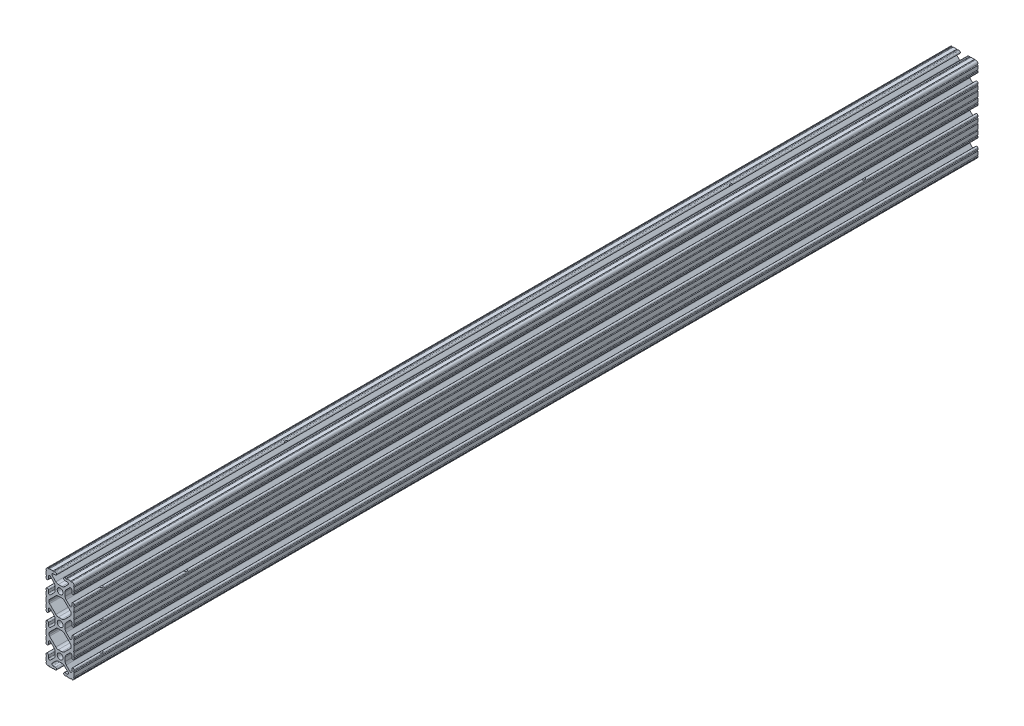
SolidWorks part; units mm, degrees
ref_plane "Front" through (0, 0, 0) normal (0, 0, 1) x (1, 0, 0)
ref_plane "Top" through (0, 0, 0) normal (0, 1, 0) x (1, 0, 0)
ref_plane "Right" through (0, 0, 0) normal (1, 0, 0) x (0, 0, -1)
sketch "Sketch1" plane through (0, 0, 0) normal (0, 0, 1) x (1, 0, 0)
  line L0 (-7.4908, -34.8742) -> (7.4908, -34.8742) construction
  line L1 (-3.1974, -36.9951) -> (3.1974, -36.9951) construction
  line L2 (-7.4908, 34.8742) -> (7.4908, 34.8742) construction
  line L3 (-3.1974, 36.9951) -> (3.1974, 36.9951) construction
  line L16 (-9.9314, -12.1463) -> (-9.9314, -13.2537)
  line L17 (-3.8759, -5.4384) -> (-9.4702, -11.0327)
  line L18 (1.6308, -4.5085) -> (-1.6308, -4.5085)
  line L19 (9.4702, -11.0327) -> (3.8759, -5.4384)
  line L20 (9.9314, -13.2537) -> (9.9314, -12.1463)
  line L21 (3.8759, -19.9616) -> (9.4702, -14.3673)
  line L22 (-1.6308, -20.8915) -> (1.6308, -20.8915)
  line L23 (-9.4702, -14.3673) -> (-3.8759, -19.9616)
  line L32 (-9.9314, 13.2537) -> (-9.9314, 12.1463)
  line L33 (-3.8759, 19.9616) -> (-9.4702, 14.3673)
  line L34 (1.6308, 20.8915) -> (-1.6308, 20.8915)
  line L35 (9.4702, 14.3673) -> (3.8759, 19.9616)
  line L36 (9.9314, 12.1463) -> (9.9314, 13.2537)
  line L37 (3.8759, 5.4384) -> (9.4702, 11.0327)
  line L38 (-1.6308, 4.5085) -> (1.6308, 4.5085)
  line L39 (-9.4702, 11.0327) -> (-3.8759, 5.4384)
  line L152 (-12.7, 34.9504) -> (-12.7, 31.7246)
  line L153 (-12.7, 30.7086) -> (-12.7, 29.7023)
  line L154 (-10.4902, 29.7023) -> (-10.4902, 31.8748)
  line L155 (-8.7558, 32.5932) -> (-5.4384, 29.2759)
  line L156 (-4.5085, 27.0308) -> (-4.5085, 23.7692)
  line L157 (-5.4384, 21.5241) -> (-8.7558, 18.2068)
  line L158 (-10.4902, 18.9252) -> (-10.4902, 21.0977)
  line L159 (-12.7, 21.0977) -> (-12.7, 20.0914)
  line L160 (-12.7, 19.0754) -> (-12.7, 15.8496)
  line L161 (-12.7, 14.8336) -> (-12.7, 10.5664)
  line L162 (-12.7, 9.5504) -> (-12.7, 6.3246)
  line L163 (-12.7, 5.3086) -> (-12.7, 4.3023)
  line L164 (-10.4902, 4.3023) -> (-10.4902, 6.4748)
  line L165 (-8.7558, 7.1932) -> (-5.4384, 3.8759)
  line L166 (-4.5085, 1.6308) -> (-4.5085, -1.6308)
  line L167 (-5.4384, -3.8759) -> (-8.7558, -7.1932)
  line L168 (-10.4902, -6.4748) -> (-10.4902, -4.3023)
  line L169 (-12.7, -4.3023) -> (-12.7, -5.3086)
  line L170 (-12.7, -6.3246) -> (-12.7, -9.5504)
  line L171 (-12.7, -10.5664) -> (-12.7, -14.8336)
  line L172 (-12.7, -15.8496) -> (-12.7, -19.0754)
  line L173 (-12.7, -20.0914) -> (-12.7, -21.0977)
  line L174 (-10.4902, -21.0977) -> (-10.4902, -18.9252)
  line L175 (-8.7558, -18.2068) -> (-5.4384, -21.5241)
  line L176 (-4.5085, -23.7692) -> (-4.5085, -27.0308)
  line L177 (-5.4384, -29.2759) -> (-8.7558, -32.5932)
  line L178 (-10.4902, -31.8748) -> (-10.4902, -29.7023)
  line L179 (-12.7, -29.7023) -> (-12.7, -30.7086)
  line L180 (-12.7, -31.7246) -> (-12.7, -34.9504)
  line L181 (-9.5504, -38.1) -> (-6.3246, -38.1)
  line L182 (-5.3086, -38.1) -> (-4.3023, -38.1)
  line L183 (-4.3023, -35.8902) -> (-6.4748, -35.8902)
  line L184 (-7.1932, -34.1558) -> (-3.8759, -30.8384)
  line L185 (-1.6308, -29.9085) -> (1.6308, -29.9085)
  line L186 (3.8759, -30.8384) -> (7.1932, -34.1558)
  line L187 (6.4748, -35.8902) -> (4.3023, -35.8902)
  line L188 (4.3023, -38.1) -> (5.3086, -38.1)
  line L189 (6.3246, -38.1) -> (9.5504, -38.1)
  line L190 (12.7, -34.9504) -> (12.7, -31.7246)
  line L191 (12.7, -30.7086) -> (12.7, -29.7023)
  line L192 (10.4902, -29.7023) -> (10.4902, -31.8748)
  line L193 (8.7558, -32.5932) -> (5.4384, -29.2759)
  line L194 (4.5085, -27.0308) -> (4.5085, -23.7692)
  line L195 (5.4384, -21.5241) -> (8.7558, -18.2068)
  line L196 (10.4902, -18.9252) -> (10.4902, -21.0977)
  line L197 (12.7, -21.0977) -> (12.7, -20.0914)
  line L198 (12.7, -19.0754) -> (12.7, -15.8496)
  line L199 (12.7, -14.8336) -> (12.7, -10.5664)
  line L200 (12.7, -9.5504) -> (12.7, -6.3246)
  line L201 (12.7, -5.3086) -> (12.7, -4.3023)
  line L202 (10.4902, -4.3023) -> (10.4902, -6.4748)
  line L203 (8.7558, -7.1932) -> (5.4384, -3.8759)
  line L204 (4.5085, -1.6308) -> (4.5085, 1.6308)
  line L205 (5.4384, 3.8759) -> (8.7558, 7.1932)
  line L206 (10.4902, 6.4748) -> (10.4902, 4.3023)
  line L207 (12.7, 4.3023) -> (12.7, 5.3086)
  line L208 (12.7, 6.3246) -> (12.7, 9.5504)
  line L209 (12.7, 10.5664) -> (12.7, 14.8336)
  line L210 (12.7, 15.8496) -> (12.7, 19.0754)
  line L211 (12.7, 20.0914) -> (12.7, 21.0977)
  line L212 (10.4902, 21.0977) -> (10.4902, 18.9252)
  line L213 (8.7558, 18.2068) -> (5.4384, 21.5241)
  line L214 (4.5085, 23.7692) -> (4.5085, 27.0308)
  line L215 (5.4384, 29.2759) -> (8.7558, 32.5932)
  line L216 (10.4902, 31.8748) -> (10.4902, 29.7023)
  line L217 (12.7, 29.7023) -> (12.7, 30.7086)
  line L218 (12.7, 31.7246) -> (12.7, 34.9504)
  line L219 (9.5504, 38.1) -> (6.3246, 38.1)
  line L220 (5.3086, 38.1) -> (4.3023, 38.1)
  line L221 (4.3023, 35.8902) -> (6.4748, 35.8902)
  line L222 (7.1932, 34.1558) -> (3.8759, 30.8384)
  line L223 (1.6308, 29.9085) -> (-1.6308, 29.9085)
  line L224 (-3.8759, 30.8384) -> (-7.1932, 34.1558)
  line L225 (-6.4748, 35.8902) -> (-4.3023, 35.8902)
  line L226 (-4.3023, 38.1) -> (-5.3086, 38.1)
  line L227 (-6.3246, 38.1) -> (-9.5504, 38.1)
  circle A2 centre (0, -25.4) radius 2.6035
  circle A4 centre (0, 0) radius 2.6035
  circle A6 centre (0, 25.4) radius 2.6035
  arc A18 (-9.9314, -13.2537) -> (-9.4702, -14.3673) centre (-8.3566, -13.2537) ccw
  arc A19 (-9.4702, -11.0327) -> (-9.9314, -12.1463) centre (-8.3566, -12.1463) ccw
  arc A20 (-1.6308, -4.5085) -> (-3.8759, -5.4384) centre (-1.6308, -7.6835) ccw
  arc A21 (3.8759, -5.4384) -> (1.6308, -4.5085) centre (1.6308, -7.6835) ccw
  arc A22 (9.9314, -12.1463) -> (9.4702, -11.0327) centre (8.3566, -12.1463) ccw
  arc A23 (9.4702, -14.3673) -> (9.9314, -13.2537) centre (8.3566, -13.2537) ccw
  arc A24 (1.6308, -20.8915) -> (3.8759, -19.9616) centre (1.6308, -17.7165) ccw
  arc A25 (-3.8759, -19.9616) -> (-1.6308, -20.8915) centre (-1.6308, -17.7165) ccw
  arc A36 (-9.9314, 12.1463) -> (-9.4702, 11.0327) centre (-8.3566, 12.1463) ccw
  arc A37 (-9.4702, 14.3673) -> (-9.9314, 13.2537) centre (-8.3566, 13.2537) ccw
  arc A38 (-1.6308, 20.8915) -> (-3.8759, 19.9616) centre (-1.6308, 17.7165) ccw
  arc A39 (3.8759, 19.9616) -> (1.6308, 20.8915) centre (1.6308, 17.7165) ccw
  arc A40 (9.9314, 13.2537) -> (9.4702, 14.3673) centre (8.3566, 13.2537) ccw
  arc A41 (9.4702, 11.0327) -> (9.9314, 12.1463) centre (8.3566, 12.1463) ccw
  arc A42 (1.6308, 4.5085) -> (3.8759, 5.4384) centre (1.6308, 7.6835) ccw
  arc A43 (-3.8759, 5.4384) -> (-1.6308, 4.5085) centre (-1.6308, 7.6835) ccw
  arc A168 (-10.5664, 38.1) -> (-12.7, 35.9664) centre (-10.592, 35.992) ccw
  arc A169 (-12.7, 34.9504) -> (-12.7, 35.9664) centre (-12.7, 35.4584) ccw
  arc A170 (-12.7, 30.7086) -> (-12.7, 31.7246) centre (-12.7, 31.2166) ccw
  arc A171 (-12.7, 29.7023) -> (-10.4902, 29.7023) centre (-11.5951, 29.7023) ccw
  arc A172 (-8.7558, 32.5932) -> (-10.4902, 31.8748) centre (-9.4742, 31.8748) ccw
  arc A173 (-4.5085, 27.0308) -> (-5.4384, 29.2759) centre (-7.6835, 27.0308) ccw
  arc A174 (-5.4384, 21.5241) -> (-4.5085, 23.7692) centre (-7.6835, 23.7692) ccw
  arc A175 (-10.4902, 18.9252) -> (-8.7558, 18.2068) centre (-9.4742, 18.9252) ccw
  arc A176 (-10.4902, 21.0977) -> (-12.7, 21.0977) centre (-11.5951, 21.0977) ccw
  arc A177 (-12.7, 19.0754) -> (-12.7, 20.0914) centre (-12.7, 19.5834) ccw
  arc A178 (-12.7, 14.8336) -> (-12.7, 15.8496) centre (-12.7, 15.3416) ccw
  arc A179 (-12.7, 9.5504) -> (-12.7, 10.5664) centre (-12.7, 10.0584) ccw
  arc A180 (-12.7, 5.3086) -> (-12.7, 6.3246) centre (-12.7, 5.8166) ccw
  arc A181 (-12.7, 4.3023) -> (-10.4902, 4.3023) centre (-11.5951, 4.3023) ccw
  arc A182 (-8.7558, 7.1932) -> (-10.4902, 6.4748) centre (-9.4742, 6.4748) ccw
  arc A183 (-4.5085, 1.6308) -> (-5.4384, 3.8759) centre (-7.6835, 1.6308) ccw
  arc A184 (-5.4384, -3.8759) -> (-4.5085, -1.6308) centre (-7.6835, -1.6308) ccw
  arc A185 (-10.4902, -6.4748) -> (-8.7558, -7.1932) centre (-9.4742, -6.4748) ccw
  arc A186 (-10.4902, -4.3023) -> (-12.7, -4.3023) centre (-11.5951, -4.3023) ccw
  arc A187 (-12.7, -6.3246) -> (-12.7, -5.3086) centre (-12.7, -5.8166) ccw
  arc A188 (-12.7, -10.5664) -> (-12.7, -9.5504) centre (-12.7, -10.0584) ccw
  arc A189 (-12.7, -15.8496) -> (-12.7, -14.8336) centre (-12.7, -15.3416) ccw
  arc A190 (-12.7, -20.0914) -> (-12.7, -19.0754) centre (-12.7, -19.5834) ccw
  arc A191 (-12.7, -21.0977) -> (-10.4902, -21.0977) centre (-11.5951, -21.0977) ccw
  arc A192 (-8.7558, -18.2068) -> (-10.4902, -18.9252) centre (-9.4742, -18.9252) ccw
  arc A193 (-4.5085, -23.7692) -> (-5.4384, -21.5241) centre (-7.6835, -23.7692) ccw
  arc A194 (-5.4384, -29.2759) -> (-4.5085, -27.0308) centre (-7.6835, -27.0308) ccw
  arc A195 (-10.4902, -31.8748) -> (-8.7558, -32.5932) centre (-9.4742, -31.8748) ccw
  arc A196 (-10.4902, -29.7023) -> (-12.7, -29.7023) centre (-11.5951, -29.7023) ccw
  arc A197 (-12.7, -31.7246) -> (-12.7, -30.7086) centre (-12.7, -31.2166) ccw
  arc A198 (-12.7, -35.9664) -> (-12.7, -34.9504) centre (-12.7, -35.4584) ccw
  arc A199 (-12.7, -35.9664) -> (-10.5664, -38.1) centre (-10.592, -35.992) ccw
  arc A200 (-9.5504, -38.1) -> (-10.5664, -38.1) centre (-10.0584, -38.1) ccw
  arc A201 (-5.3086, -38.1) -> (-6.3246, -38.1) centre (-5.8166, -38.1) ccw
  arc A202 (-4.3023, -38.1) -> (-4.3023, -35.8902) centre (-4.3023, -36.9951) ccw
  arc A203 (-7.1932, -34.1558) -> (-6.4748, -35.8902) centre (-6.4748, -34.8742) ccw
  arc A204 (-1.6308, -29.9085) -> (-3.8759, -30.8384) centre (-1.6308, -33.0835) ccw
  arc A205 (3.8759, -30.8384) -> (1.6308, -29.9085) centre (1.6308, -33.0835) ccw
  arc A206 (6.4748, -35.8902) -> (7.1932, -34.1558) centre (6.4748, -34.8742) ccw
  arc A207 (4.3023, -35.8902) -> (4.3023, -38.1) centre (4.3023, -36.9951) ccw
  arc A208 (6.3246, -38.1) -> (5.3086, -38.1) centre (5.8166, -38.1) ccw
  arc A209 (10.5664, -38.1) -> (9.5504, -38.1) centre (10.0584, -38.1) ccw
  arc A210 (10.5664, -38.1) -> (12.7, -35.9664) centre (10.592, -35.992) ccw
  arc A211 (12.7, -34.9504) -> (12.7, -35.9664) centre (12.7, -35.4584) ccw
  arc A212 (12.7, -30.7086) -> (12.7, -31.7246) centre (12.7, -31.2166) ccw
  arc A213 (12.7, -29.7023) -> (10.4902, -29.7023) centre (11.5951, -29.7023) ccw
  arc A214 (8.7558, -32.5932) -> (10.4902, -31.8748) centre (9.4742, -31.8748) ccw
  arc A215 (4.5085, -27.0308) -> (5.4384, -29.2759) centre (7.6835, -27.0308) ccw
  arc A216 (5.4384, -21.5241) -> (4.5085, -23.7692) centre (7.6835, -23.7692) ccw
  arc A217 (10.4902, -18.9252) -> (8.7558, -18.2068) centre (9.4742, -18.9252) ccw
  arc A218 (10.4902, -21.0977) -> (12.7, -21.0977) centre (11.5951, -21.0977) ccw
  arc A219 (12.7, -19.0754) -> (12.7, -20.0914) centre (12.7, -19.5834) ccw
  arc A220 (12.7, -14.8336) -> (12.7, -15.8496) centre (12.7, -15.3416) ccw
  arc A221 (12.7, -9.5504) -> (12.7, -10.5664) centre (12.7, -10.0584) ccw
  arc A222 (12.7, -5.3086) -> (12.7, -6.3246) centre (12.7, -5.8166) ccw
  arc A223 (12.7, -4.3023) -> (10.4902, -4.3023) centre (11.5951, -4.3023) ccw
  arc A224 (8.7558, -7.1932) -> (10.4902, -6.4748) centre (9.4742, -6.4748) ccw
  arc A225 (4.5085, -1.6308) -> (5.4384, -3.8759) centre (7.6835, -1.6308) ccw
  arc A226 (5.4384, 3.8759) -> (4.5085, 1.6308) centre (7.6835, 1.6308) ccw
  arc A227 (10.4902, 6.4748) -> (8.7558, 7.1932) centre (9.4742, 6.4748) ccw
  arc A228 (10.4902, 4.3023) -> (12.7, 4.3023) centre (11.5951, 4.3023) ccw
  arc A229 (12.7, 6.3246) -> (12.7, 5.3086) centre (12.7, 5.8166) ccw
  arc A230 (12.7, 10.5664) -> (12.7, 9.5504) centre (12.7, 10.0584) ccw
  arc A231 (12.7, 15.8496) -> (12.7, 14.8336) centre (12.7, 15.3416) ccw
  arc A232 (12.7, 20.0914) -> (12.7, 19.0754) centre (12.7, 19.5834) ccw
  arc A233 (12.7, 21.0977) -> (10.4902, 21.0977) centre (11.5951, 21.0977) ccw
  arc A234 (8.7558, 18.2068) -> (10.4902, 18.9252) centre (9.4742, 18.9252) ccw
  arc A235 (4.5085, 23.7692) -> (5.4384, 21.5241) centre (7.6835, 23.7692) ccw
  arc A236 (5.4384, 29.2759) -> (4.5085, 27.0308) centre (7.6835, 27.0308) ccw
  arc A237 (10.4902, 31.8748) -> (8.7558, 32.5932) centre (9.4742, 31.8748) ccw
  arc A238 (10.4902, 29.7023) -> (12.7, 29.7023) centre (11.5951, 29.7023) ccw
  arc A239 (12.7, 31.7246) -> (12.7, 30.7086) centre (12.7, 31.2166) ccw
  arc A240 (12.7, 35.9664) -> (12.7, 34.9504) centre (12.7, 35.4584) ccw
  arc A241 (12.7, 35.9664) -> (10.5664, 38.1) centre (10.592, 35.992) ccw
  arc A242 (9.5504, 38.1) -> (10.5664, 38.1) centre (10.0584, 38.1) ccw
  arc A243 (5.3086, 38.1) -> (6.3246, 38.1) centre (5.8166, 38.1) ccw
  arc A244 (4.3023, 38.1) -> (4.3023, 35.8902) centre (4.3023, 36.9951) ccw
  arc A245 (7.1932, 34.1558) -> (6.4748, 35.8902) centre (6.4748, 34.8742) ccw
  arc A246 (1.6308, 29.9085) -> (3.8759, 30.8384) centre (1.6308, 33.0835) ccw
  arc A247 (-3.8759, 30.8384) -> (-1.6308, 29.9085) centre (-1.6308, 33.0835) ccw
  arc A248 (-6.4748, 35.8902) -> (-7.1932, 34.1558) centre (-6.4748, 34.8742) ccw
  arc A249 (-4.3023, 35.8902) -> (-4.3023, 38.1) centre (-4.3023, 36.9951) ccw
  arc A250 (-6.3246, 38.1) -> (-5.3086, 38.1) centre (-5.8166, 38.1) ccw
  arc A251 (-10.5664, 38.1) -> (-9.5504, 38.1) centre (-10.0584, 38.1) ccw
extrude "Boss-Extrude1" add sketch "Sketch1" along normal mid plane 812.8
sketch "Sketch2" plane through (4.5085, 0, 0) normal (1, 0, 0) x (0, 0, -1)
  line L0 (-406.4, 38.1) -> (406.4, 38.1) construction
  line L1 (-406.4, 23.7692) -> (-406.4, 27.0308) construction
  line L2 (-406.4, -1.6308) -> (-406.4, 1.6308) construction
  line L3 (-406.4, -27.0308) -> (-406.4, -23.7692) construction
  circle A0 centre (-381, 25.4) radius 3.5
  circle A1 centre (-381, 0) radius 3.5
  circle A2 centre (-381, -25.4) radius 3.5
  dimension "D1" = 7
  dimension "D2" = 12.7
  dimension "D3" = 25.4
  dimension "D4" = 7
  dimension "D5" = 7
  dimension "D6" = 25.4
  dimension "D7" = 25.4
  dimension "D8" = 25.4
  dimension "D9" = 25.4
extrude "Cut-Extrude1" cut sketch "Sketch2" against normal through all both and the other way through all
sketch "Sketch3" plane through (4.5085, 0, 0) normal (1, 0, 0) x (0, 0, -1)
  line L0 (0, 0) -> (0, 69.8838) construction
  line L1 (-406.4, -1.6308) -> (-406.4, 1.6308) construction
  line L2 (-406.4, 38.1) -> (406.4, 38.1) construction
  circle A0 centre (-304.8, 0) radius 3.5
  circle A1 centre (304.8, 0) radius 3.5
  dimension "D1" = 7
  dimension "D2" = 101.6
  dimension "D3" = 38.1
extrude "Cut-Extrude2" cut sketch "Sketch3" against normal through all both and the other way through all
sketch "Sketch4" plane through (0, -29.9085, 0) normal (0, -1, 0) x (1, 0, 0)
  line L0 (0, 0) -> (131.3157, 0) construction
  circle A0 centre (0, 200) radius 3.5
  circle A1 centre (0, -200) radius 3.5
  dimension "D1" = 7
  dimension "D2" = 200
extrude "Cut-Extrude3" cut sketch "Sketch4" against normal through all both and the other way through all
